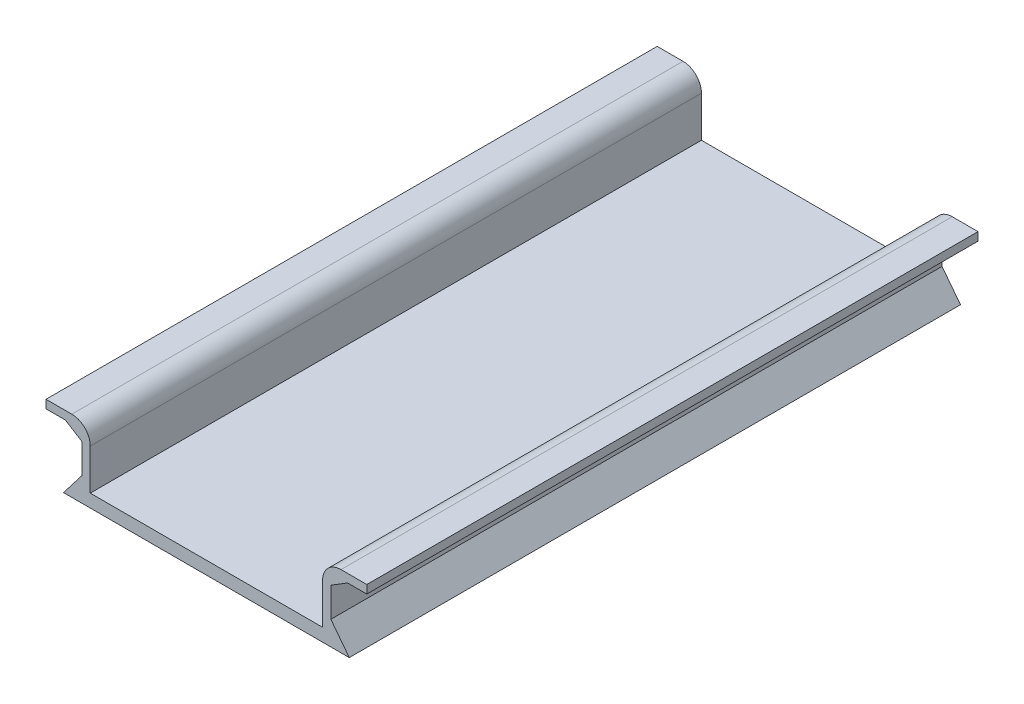
SolidWorks part; units mm, degrees
ref_plane "Front Plane" through (0, 0, 0) normal (0, 0, 1) x (1, 0, 0)
ref_plane "Top Plane" through (0, 0, 0) normal (0, 1, 0) x (1, 0, 0)
ref_plane "Right Plane" through (0, 0, 0) normal (1, 0, 0) x (0, 0, -1)
sketch "Sketch1" plane through (0, 0, 0) normal (0, 0, 1) x (1, 0, 0)
  line L0 (-15.5, 0) -> (15.5, 0)
  line L1 (15.5, 0) -> (13.5, 2.6)
  line L2 (13.5, 2.6) -> (13.5, 5.8)
  line L3 (13.5, 5.8) -> (15.3, 6.92)
  line L4 (15.3, 6.92) -> (17.4, 6.92)
  line L5 (17.4, 6.92) -> (17.4, 7.82)
  line L6 (17.4, 7.82) -> (14.6, 7.82)
  line L7 (12.6, 5.82) -> (12.6, 1.4)
  line L8 (12.6, 1.4) -> (-12.6, 1.4)
  line L9 (0, 1.4) -> (0, 0) construction
  line L10 (-15.5, 0) -> (-13.5, 2.6)
  line L11 (-17.4, 6.92) -> (-17.4, 7.82)
  line L12 (-15.3, 6.92) -> (-17.4, 6.92)
  line L13 (-17.4, 7.82) -> (-14.6, 7.82)
  line L14 (-13.5, 5.8) -> (-15.3, 6.92)
  line L15 (-13.5, 2.6) -> (-13.5, 5.8)
  line L16 (-12.6, 5.82) -> (-12.6, 1.4)
  arc A0 (14.6, 7.82) -> (12.6, 5.82) centre (14.6, 5.82) ccw
  arc A1 (-14.6, 7.82) -> (-12.6, 5.82) centre (-14.6, 5.82) cw
  point P0 (0, 1.4)
  point P4 (0, 0)
  point P17 (12.6, 7.82)
  dimension "D11" = 2
  dimension "D1" = 31
  dimension "D2" = 1.4
  dimension "D3" = 2.6
  dimension "D4" = 2
  dimension "D5" = 0.9
  dimension "D6" = 0.9
  dimension "D7" = 4.8
  dimension "D8" = 2.1
  dimension "D9" = 7.82
  dimension "D10" = 3.2
extrude "Boss-Extrude1" add sketch "Sketch1" along normal blind 66.3
